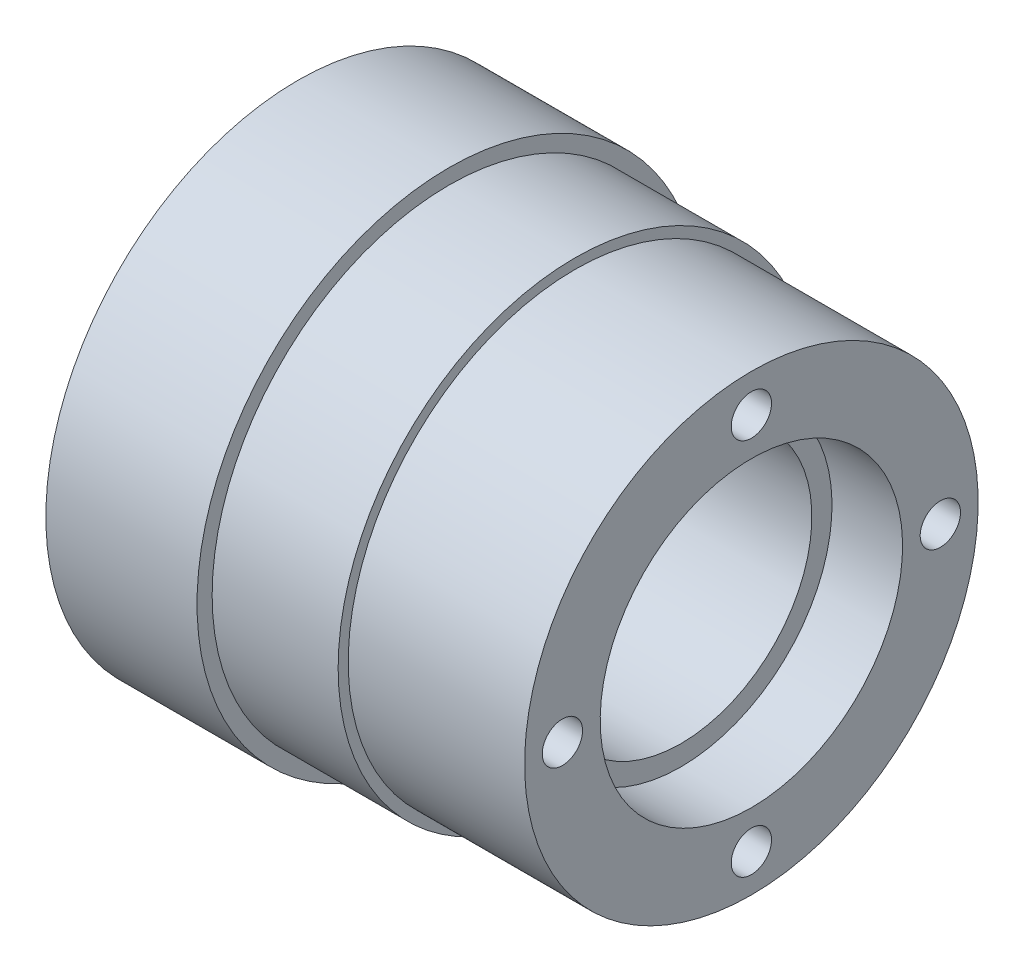
SolidWorks part; units mm, degrees
material "2024-T4"
ref_plane "Front Plane" through (0, 0, 0) normal (0, 0, 1) x (1, 0, 0)
ref_plane "Top Plane" through (0, 0, 0) normal (0, 1, 0) x (1, 0, 0)
ref_plane "Right Plane" through (0, 0, 0) normal (1, 0, 0) x (0, 0, -1)
sketch "Sketch1" plane through (0, 0, 0) normal (0, 0, 1) x (1, 0, 0)
  line L0 (-22.5, 0) -> (22.5, 0) construction
  line L1 (-22.5, 13.5) -> (-18.3, 13.5)
  line L2 (-18.3, 13.5) -> (-18.3, 13)
  line L3 (-18.3, 13) -> (15.5, 13)
  line L4 (15.5, 13) -> (15.5, 15)
  line L5 (15.5, 15) -> (22.5, 15)
  line L6 (22.5, 15) -> (22.5, 22.5)
  line L7 (22.5, 22.5) -> (5, 22.5)
  line L8 (5, 22.5) -> (5, 23.5)
  line L9 (5, 23.5) -> (-7.5, 23.5)
  line L10 (-7.5, 23.5) -> (-7.5, 25)
  line L11 (-7.5, 25) -> (-22.5, 25)
  line L12 (-22.5, 25) -> (-22.5, 13.5)
  point P4 (0, 0)
  point P21 (5, 23)
  dimension "D1" = 45
  dimension "D2" = 7
  dimension "D3" = 26
  dimension "D4" = 27
  dimension "D5" = 30
  dimension "D6" = 4.2
  dimension "D7" = 50
  dimension "D8" = 45
  dimension "D9" = 47
  dimension "D10" = 15
  dimension "D11" = 17.5
revolve "Revolve1" add sketch "Sketch1" angle 360 about L0
sketch "Sketch2" plane through (22.5, 0, 0) normal (1, 0, 0) x (0, 0, -1)
  line L0 (0, 22.5) -> (0, 15) construction
  circle A0 centre (0, 18.75) radius 2
  circle A1 centre (0, 0) radius 22.5 construction
  circle A2 centre (0, 0) radius 22.5 construction
  circle A3 centre (0, 0) radius 15 construction
  circle A4 centre (18.75, 0) radius 2
  circle A5 centre (0, -18.75) radius 2
  circle A6 centre (-18.75, 0) radius 2
  point P21 (0, 0)
  dimension "D1" = 4
  dimension "D2" = 18.75
  dimension "D3" = 18.75
extrude "Cut-Extrude1" cut sketch "Sketch2" against normal blind 10
sketch "Sketch3" plane through (-22.5, 0, 0) normal (-1, 0, 0) x (0, 0, 1)
  line L0 (0, 13.5) -> (0, 25) construction
  circle A0 centre (0, 0) radius 13.5 construction
  circle A1 centre (0, 0) radius 13.5 construction
  circle A2 centre (0, 0) radius 25 construction
  circle A3 centre (0, 19.25) radius 2
  circle A4 centre (19.25, 0) radius 2
  circle A5 centre (0, -19.25) radius 2
  circle A6 centre (-19.25, 0) radius 2
  point P19 (0, 0)
  dimension "D1" = 4
  dimension "D2" = 19.25
  dimension "D3" = 19.25
extrude "Cut-Extrude2" cut sketch "Sketch3" against normal blind 10
equation "\"mini-flipper-shaft-diameter\"= 26mm"
equation "\"mini-shaft-ring-groove-diam\"= 7.8mm"
equation "\"mini-shaft-ring-groove-width\"= 1mm"
equation "\"dtCoverPlate-DistFrom-GearCent\"= 73mm"
equation "\"wormGearShaft-L\"= \"dtCoverPlate-DistFrom-GearCent\" - 27.75 + 3.75"
equation "\"wormGearShaft-Dsmall\"= 6mm"
equation "\"wormGearShaft-Dworm\"= 12mm"
equation "\"wormL-D\" = 12mm"
equation "\"wormR-D\" = 15mm"
equation "\"wormGearL-D\" = 46mm"
equation "\"wormGearR-D\" = 50mm"
equation "\"D7@Sketch1\"=\"wormGearR-D\""
